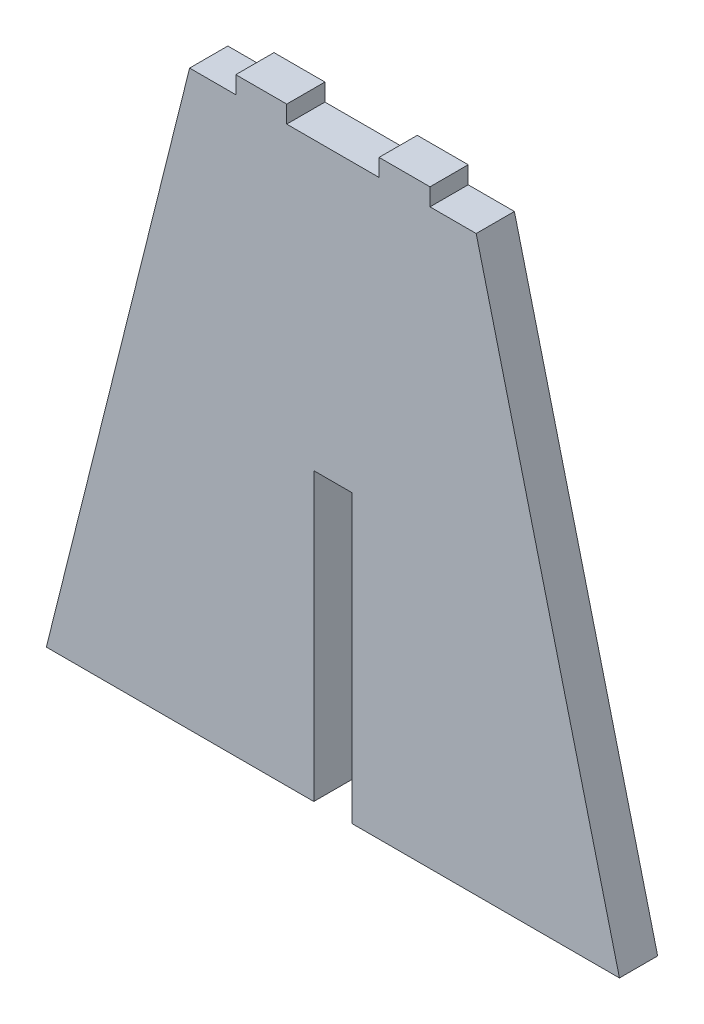
SolidWorks part; units mm, degrees
ref_plane "Front Plane" through (0, 0, 0) normal (0, 0, 1) x (1, 0, 0)
ref_plane "Top Plane" through (0, 0, 0) normal (0, 1, 0) x (1, 0, 0)
ref_plane "Right Plane" through (0, 0, 0) normal (1, 0, 0) x (0, 0, -1)
sketch "Sketch2" plane through (0, 0, 0) normal (0, 0, 1) x (1, 0, 0)
  line L0 (104.8846, 0) -> (0, 0) construction
  line L1 (-108.6923, 0) -> (0, 0) construction
  line L2 (0, 0) -> (0, 106.4423) construction
  line L3 (0, 0) -> (0, -93.6346) construction
  line L4 (45, 9.8654) -> (3, 9.8654)
  line L5 (-45, 9.8654) -> (-22.5, 99.8654)
  line L6 (-22.5, 99.8654) -> (-15.25, 99.8654)
  line L7 (22.5, 99.8654) -> (45, 9.8654)
  line L8 (11.25, 104.4253) -> (11.25, 94.3369) construction
  line L9 (-11.25, 104.4253) -> (-11.25, 94.3369) construction
  line L10 (-7.25, 102.5938) -> (-15.25, 102.5938)
  line L12 (7.25, 99.8654) -> (7.25, 102.5938)
  line L13 (7.25, 102.5938) -> (15.25, 102.5938)
  line L14 (15.25, 99.8654) -> (15.25, 102.5938)
  line L15 (6.2186, 54.8654) -> (-8.2199, 54.8654) construction
  line L16 (6.2186, 32.3654) -> (-8.2199, 32.3654) construction
  line L21 (-15.25, 99.8654) -> (-15.25, 102.5938)
  line L23 (-7.25, 99.8654) -> (-7.25, 102.5938)
  line L24 (-7.25, 99.8654) -> (7.25, 99.8654)
  line L25 (15.25, 99.8654) -> (22.5, 99.8654)
  line L26 (-3, 9.8654) -> (-45, 9.8654)
  line L27 (3, 54.8654) -> (-3, 54.8654)
  line L28 (3, 54.8654) -> (3, 9.8654)
  line L30 (-3, 54.8654) -> (-3, 9.8654)
  point P14 (11.25, 99.8654)
  point P19 (-11.25, 99.8654)
  point P28 (0, 32.3654)
  dimension "D1" = 90
  dimension "D2" = 90
  dimension "D3" = 45
  dimension "D4" = 45
  dimension "D5" = 11.25
  dimension "D6" = 11.25
  dimension "D7" = 4
  dimension "D8" = 4
  dimension "D9" = 11.25
  dimension "D10" = 22.5
  dimension "D11" = 45
  dimension "D12" = 22.5
  dimension "D13" = 6
extrude "Boss-Extrude4" add sketch "Sketch2" along normal blind 6
